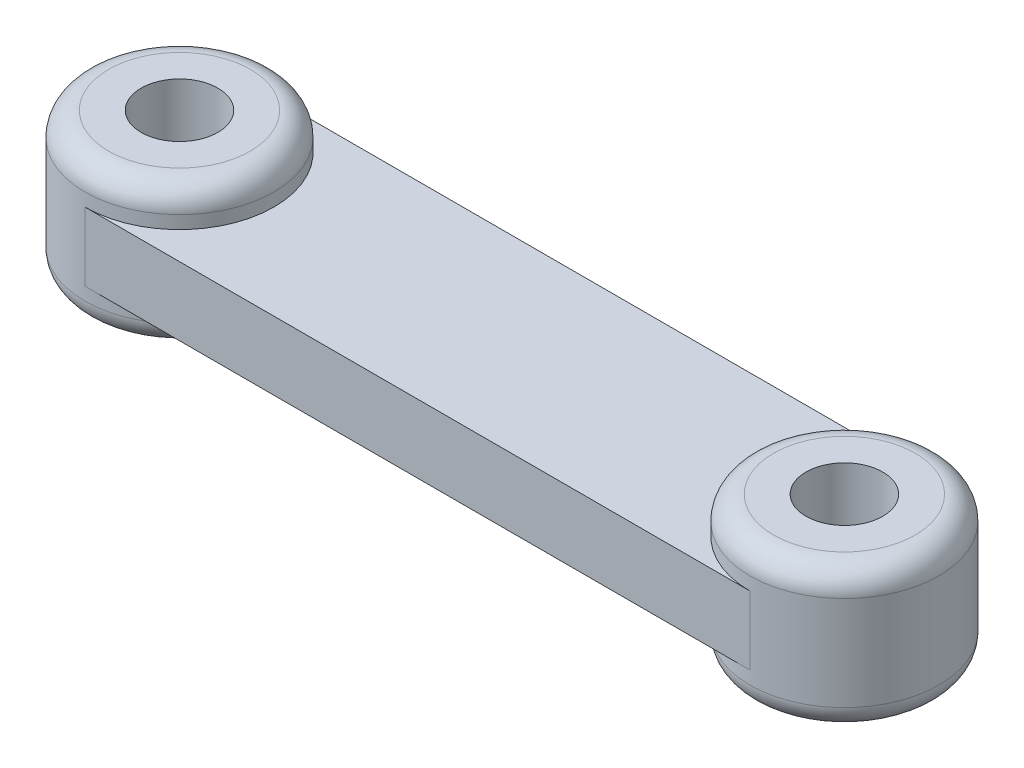
SolidWorks part; units mm, degrees
ref_plane "Front Plane" through (0, 0, 0) normal (0, 0, 1) x (1, 0, 0)
ref_plane "Top Plane" through (0, 0, 0) normal (0, 1, 0) x (1, 0, 0)
ref_plane "Right Plane" through (0, 0, 0) normal (1, 0, 0) x (0, 0, -1)
sketch "Sketch1" plane through (0, 0, 0) normal (0, 1, 0) x (1, 0, 0)
  line L0 (-14.075, 0) -> (14.075, 0) construction
  line L1 (-14.075, 4) -> (14.075, 4)
  line L2 (-14.075, -4) -> (14.075, -4)
  arc A0 (-14.075, 4) -> (-14.075, -4) centre (-14.075, 0) ccw
  arc A1 (14.075, -4) -> (14.075, 4) centre (14.075, 0) ccw
  point P2 (0, 0)
  point P7 (18.075, 0)
  point P8 (-18.075, 0)
  dimension "D1" = 8
  dimension "D2" = 28.15
extrude "Boss-Extrude1" add sketch "Sketch1" along normal mid plane 2.9
sketch "Sketch2" plane through (0, 0, 0) normal (0, 1, 0) x (1, 0, 0)
  circle A0 centre (-14.075, 0) radius 4
  circle A1 centre (14.075, 0) radius 4
extrude "Boss-Extrude2" add sketch "Sketch2" along normal mid plane 6
fillet "Fillet1" radius 1 4 edges at (14.075, 3, 4) (14.075, -3, 4) (-14.075, -3, 4) (-14.075, 3, 4)
sketch "Sketch3" plane through (0, 3, 0) normal (0, 1, 0) x (1, 0, 0)
  circle A0 centre (-14.075, 0) radius 1.625
  circle A1 centre (14.075, 0) radius 1.625
  circle A2 centre (-14.075, 0) radius 3 construction
  circle A3 centre (14.075, 0) radius 3 construction
  dimension "D1" = 3.25
extrude "Cut-Extrude1" cut sketch "Sketch3" against normal through all
